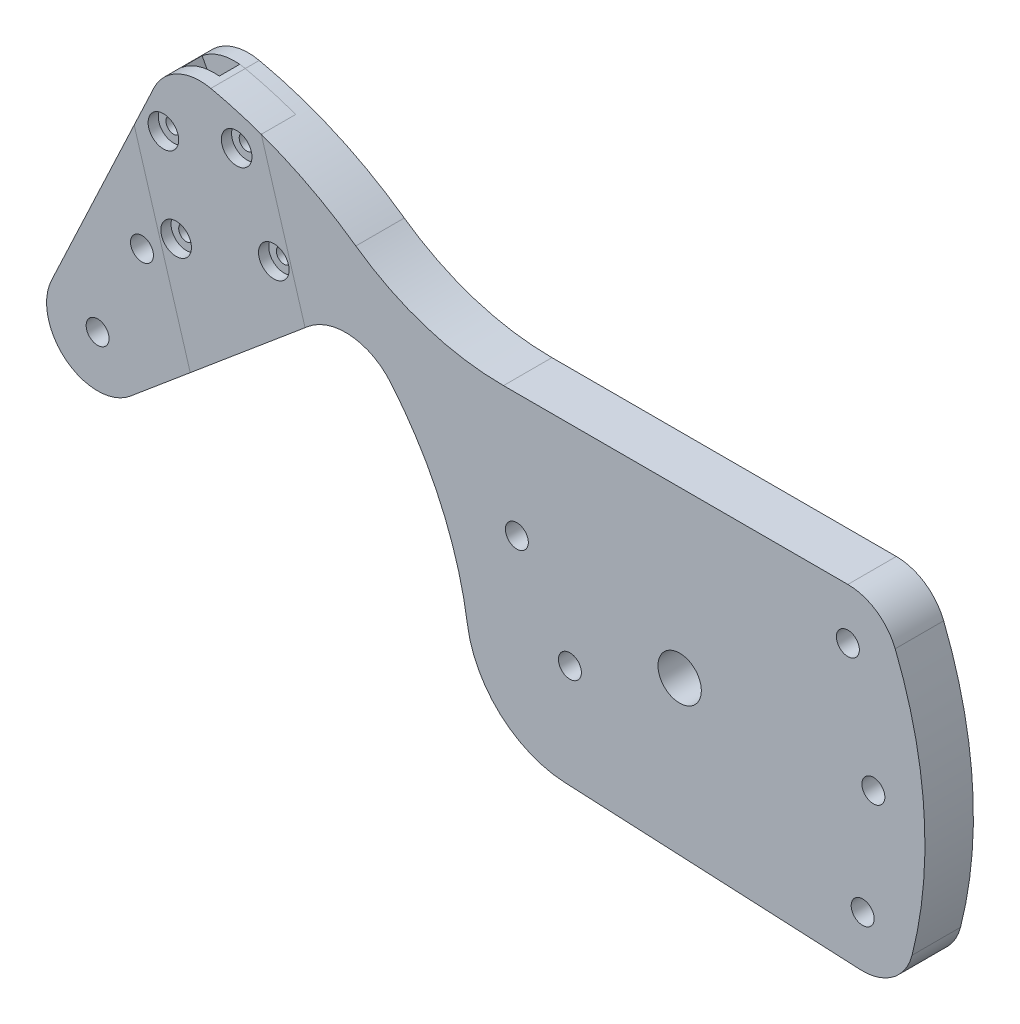
SolidWorks part; units mm, degrees
ref_plane "Front Plane" through (0, 0, 0) normal (0, 0, 1) x (1, 0, 0)
ref_plane "Top Plane" through (0, 0, 0) normal (0, 1, 0) x (1, 0, 0)
ref_plane "Right Plane" through (0, 0, 0) normal (1, 0, 0) x (0, 0, -1)
sketch "Sketch1" plane through (0, 0, 0) normal (0, 0, 1) x (1, 0, 0)
  line L1 (-4.25, -4.25) -> (4.25, -4.25) construction
  line L2 (-4.25, -4.25) -> (-4.25, 4.25) construction
  line L3 (-4.25, 4.25) -> (4.25, 4.25) construction
  line L4 (4.25, -4.25) -> (4.25, 4.25) construction
  line L5 (-4.25, -4.25) -> (4.25, 4.25) construction
  line L6 (-4.25, 4.25) -> (4.25, -4.25) construction
  line L7 (35.3984, -31.7883) -> (-22.5002, -28.984)
  line L9 (-114.4671, 24.4556) -> (-123.1671, 5.9556)
  line L10 (-107.6899, -5.9604) -> (-72.8648, 23.2613)
  line L11 (-114.4671, 24.4556) -> (-103.0859, 48.6569)
  line L16 (-65.4725, 14.4515) -> (-108.3178, -21.5) construction
  line L17 (50.9822, -33.5) -> (-177.2181, -33.5) construction
  line L20 (-34.5382, 32.4) -> (32.9822, 32.4)
  circle A0 centre (0, 0) radius 4.25
  circle A1 centre (-31.9178, 8.2) radius 2.25
  circle A2 centre (-21.5178, -8.7) radius 2.25
  circle A3 centre (32.9822, 22.4) radius 2.25
  circle A4 centre (37.9822, -0.1) radius 2.25
  circle A5 centre (35.8822, -21.8) radius 2.25
  circle A6 centre (35.8822, -21.8) radius 2.25 construction
  circle A7 centre (37.9822, -0.1) radius 2.25 construction
  circle A8 centre (32.9822, 22.4) radius 2.25 construction
  circle A9 centre (-31.9178, 8.2) radius 2.25 construction
  circle A10 centre (-21.5178, -8.7) radius 2.25 construction
  arc A12 (-41.6083, -11.6627) -> (-22.5002, -28.984) centre (-21.5178, -8.7) ccw
  arc A13 (32.5913, -31.6523) -> (28.0429, 32.4) centre (-33.3577, -4.1478) ccw construction
  arc A14 (45.5723, -24.2704) -> (42.2664, 26.1153) centre (-33.3577, -4.1478) ccw
  arc A15 (35.3984, -31.7883) -> (45.5723, -24.2704) centre (35.8822, -21.8) ccw
  arc A16 (42.2664, 26.1153) -> (32.9822, 32.4) centre (32.9822, 22.4) ccw
  circle A17 centre (-105.4178, 20.2) radius 2.25
  circle A18 centre (-33.3577, -4.1478) radius 81.4546 construction
  circle A19 centre (-114.1178, 1.7) radius 2.25
  circle A21 centre (-105.4178, 20.2) radius 2.25 construction
  circle A22 centre (-114.1178, 1.7) radius 2.25 construction
  circle A23 centre (-105.4178, 20.2) radius 10 construction
  arc A24 (-123.1671, 5.9556) -> (-107.6899, -5.9604) centre (-114.1178, 1.7) ccw
  arc A27 (-91.9187, 54.1744) -> (-103.0859, 48.6569) centre (-94.0366, 44.4013) ccw
  circle A31 centre (-33.3577, -4.1478) radius 71.4546 construction
  arc A32 (-41.6083, -11.6627) -> (-56.6627, 21.8438) centre (-108.3178, -21.5) ccw
  arc A33 (-31.0568, -26.628) -> (-91.9187, 54.1744) centre (-108.3178, -21.5) ccw
  arc A34 (-63.487, 41.6328) -> (-34.5382, 32.4) centre (-34.5382, 82.4) ccw
  arc A35 (-56.6627, 21.8438) -> (-72.8648, 23.2613) centre (-65.4725, 14.4515) ccw
  circle A36 centre (-65.4725, 14.4515) radius 10.5004 construction
  circle A37 centre (-108.3178, -21.5) radius 67.4309 construction
  circle A38 centre (-108.3178, -21.5) radius 77.4309 construction
  circle A39 centre (-108.3178, -21.5) radius 10.5004 construction
  circle A40 centre (-108.3178, -21.5) radius 11.5004 construction
  circle A41 centre (0, 0) radius 33 construction
  point P35 (50.3427, -4.5217)
  point P37 (37.1696, 16.7103)
  point P54 (-36.0565, -0.0269)
  point P75 (-40.8381, -1.4887)
  dimension "D1" = 8.5
  dimension "D3" = 10
  dimension "D5" = 50
  dimension "D7" = 40
  dimension "D4" = 10
  dimension "D2" = 10
  dimension "D8" = 1
extrude "Boss-Extrude1" add sketch "Sketch1" along normal mid plane 9.5 contours A0 L4 L3 | A0 L1 L4 | A0 L2 L1 | A0 L3 L2 | A35 A32 A12 A33 A27 L11 L9 A24 L10 A17 A19 region at (4.1562, 2.3635, 0) region at (-82.595, 21.4109, 0)
sketch "Sketch2" plane through (0, 0, 0) normal (0, 0, 1) x (1, 0, 0)
  line L0 (-94.0366, 44.4013) -> (-96.9145, 53.9782) construction
  line L1 (-78.2271, 18.7618) -> (-72.8648, 23.2613)
  line L2 (-94.0366, 44.4013) -> (-84.6999, 13.3304) construction
  line L3 (-92.0846, 44.9879) -> (-78.2271, 18.7618)
  line L4 (-95.0124, 54.3536) -> (-94.0366, 44.4013) construction
  line L5 (-94.0366, 44.4013) -> (-90.5122, 8.4534) construction
  line L6 (-98.7084, 53.2429) -> (-94.0366, 44.4013) construction
  line L7 (-94.0366, 44.4013) -> (-79.7943, 17.4467) construction
  line L8 (-100.3823, 52.1299) -> (-95.9887, 43.8147)
  line L9 (-93.0022, 54.3476) -> (-92.0846, 44.9879)
  line L12 (-92.369, 6.8953) -> (-78.2271, 18.7618)
  line L13 (-107.6899, -5.9604) -> (-72.8648, 23.2613) construction
  line L14 (-101.3327, 53.9285) -> (-91.0539, 34.4751) construction
  line L15 (-93.2007, 56.3721) -> (-91.0539, 34.4751) construction
  line L16 (-95.9887, 43.8147) -> (-92.369, 6.8953)
  line L18 (-97.0194, 54.3274) -> (-78.2271, 18.7618) construction
  line L19 (-97.0194, 54.3274) -> (-92.369, 6.8953) construction
  line L20 (-92.369, 6.8953) -> (-107.6899, -5.9604)
  line L22 (-94.0366, 44.4013) -> (-90.3786, 7.0905) construction
  line L23 (-94.0366, 44.4013) -> (-79.9955, 17.8274) construction
  arc A0 (-93.0022, 54.3476) -> (-100.3823, 52.1299) centre (-94.0366, 44.4013) ccw
  arc A1 (-95.0124, 54.3536) -> (-98.7084, 53.2429) centre (-94.0366, 44.4013) ccw construction
  arc A2 (-93.2007, 56.3721) -> (-101.3327, 53.9285) centre (-94.0366, 44.4013) ccw construction
  arc A3 (-91.9187, 54.1744) -> (-103.0859, 48.6569) centre (-94.0366, 44.4013) ccw construction
  point P33 (-96.9145, 53.9782)
  dimension "D3" = 7
  dimension "D4" = 20
  dimension "D1" = 2
  dimension "D2" = 2
extrude "Cut-Extrude1" cut sketch "Sketch2" against normal mid plane 4 contours A0 L8 L12 L9 region at (-89.8285, 28.8905, 0)
ref_plane "Plane1" through (-20.0256, 66.6414, 0) normal (-0.2878, 0.9577, 0) x (0.9577, 0.2878, 0)
sketch "Sketch4" plane through (0, 0, 4.75) normal (0, 0, 1) x (1, 0, 0)
  line L10 (-101.2193, 42.2429) -> (-86.8539, 46.5597) construction
  line L11 (-17.9186, 67.2745) -> (-22.1325, 66.0083) construction
  line L12 (-98.7212, 25.2426) -> (-79.5673, 30.9983) construction
  line L13 (-94.0366, 44.4013) -> (-89.1443, 28.1205) construction
  line L15 (-92.0846, 44.9879) -> (-93.0022, 54.3476)
  line L16 (-78.2271, 18.7618) -> (-92.0846, 44.9879)
  line L17 (-92.369, 6.8953) -> (-78.2271, 18.7618)
  line L18 (-95.9887, 43.8147) -> (-92.369, 6.8953)
  line L19 (-100.3823, 52.1299) -> (-95.9887, 43.8147)
  line L20 (-92.0846, 44.9879) -> (-93.0022, 54.3476) construction
  line L21 (-78.2271, 18.7618) -> (-92.0846, 44.9879) construction
  line L22 (-92.369, 6.8953) -> (-78.2271, 18.7618) construction
  line L23 (-95.9887, 43.8147) -> (-92.369, 6.8953) construction
  line L24 (-100.3823, 52.1299) -> (-95.9887, 43.8147) construction
  circle A0 centre (-98.7212, 25.2426) radius 1.5
  circle A1 centre (-101.2193, 42.2429) radius 1.5
  circle A2 centre (-86.8539, 46.5597) radius 1.5
  circle A3 centre (-79.5673, 30.9983) radius 1.5
  arc A7 (-93.0022, 54.3476) -> (-100.3823, 52.1299) centre (-94.0366, 44.4013) ccw
  arc A8 (-93.0022, 54.3476) -> (-100.3823, 52.1299) centre (-94.0366, 44.4013) ccw construction
  point P13 (-94.0366, 44.4013)
  dimension "D3" = 3
  dimension "D2" = 17
  dimension "D4" = 15
  dimension "D5" = 20
  dimension "D1" = 0
extrude "Cut-Extrude2" cut sketch "Sketch4" against normal through all
sketch "Sketch5" plane through (0, 0, 4.75) normal (0, 0, 1) x (1, 0, 0)
  circle A49 centre (-101.2193, 42.2429) radius 3
  circle A50 centre (-86.8539, 46.5597) radius 3
  circle A51 centre (-79.5673, 30.9983) radius 3
  circle A52 centre (-98.7212, 25.2426) radius 3
  dimension "D1" = 6
extrude "Cut-Extrude3" cut sketch "Sketch5" against normal blind 2
sketch "Sketch3" plane through (-20.0256, 66.6414, 0) normal (-0.2878, 0.9577, 0) x (0.9577, 0.2878, 0)
  line L0 (-90.7804, 2) -> (-63.7804, 2)
  line L1 (-63.7804, 2) -> (-63.7804, -4.75)
  line L2 (-72.4396, -4.75) -> (-48.8199, -4.75) construction
  line L3 (-90.7804, 2) -> (-90.7804, -4.75)
  line L4 (-116.2426, -4.75) -> (-84.7222, -4.75) construction
  line L11 (-79.3187, 2) -> (-75.2421, 2) construction
  point P3 (-77.2804, 2)
  point P11 (-77.2804, 2)
  dimension "D1" = 27
split "Split3" trim tools "Sketch3" bodies to split 111 resulting bodies 112 113
